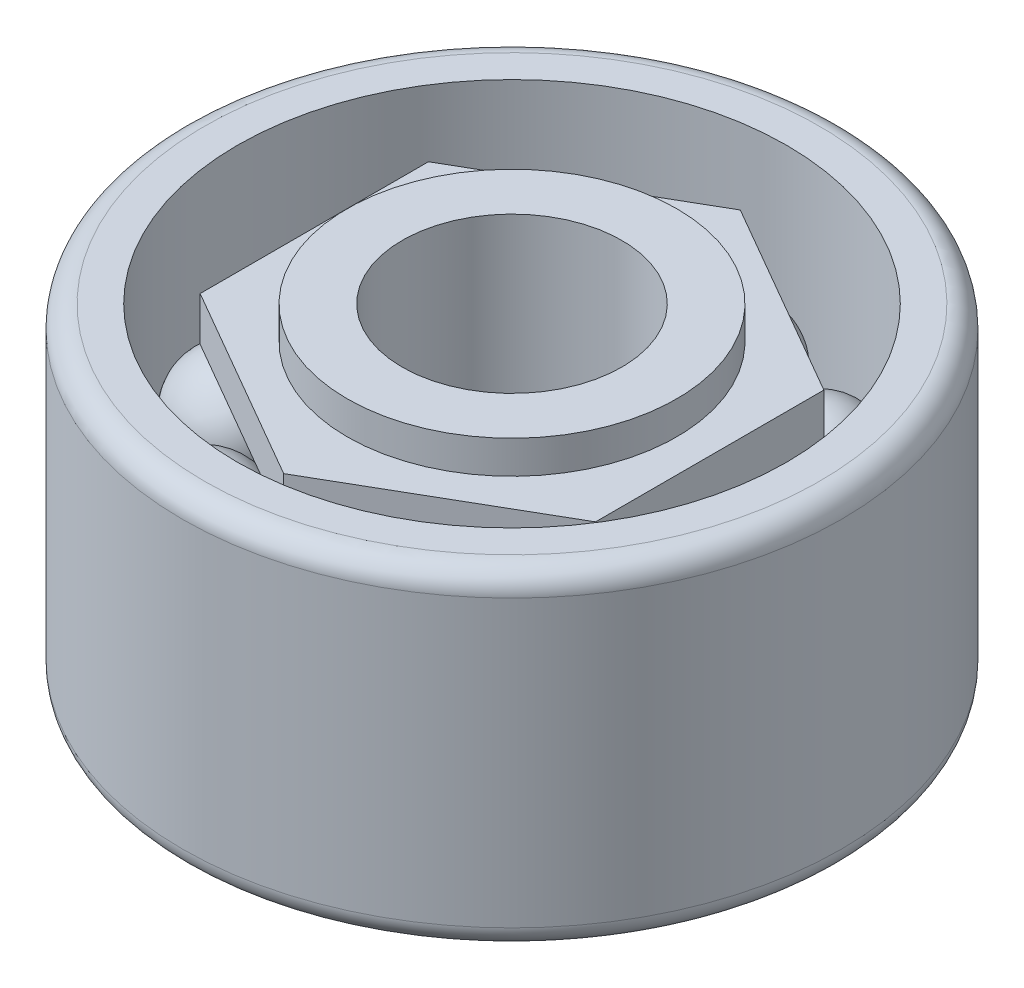
SolidWorks part; units mm, degrees
note: The reader was unsure of these and kept them because the rebuilt part matched: shared geometry of "Sketch1<3>", "Sketch1<4>".
ref_plane "Front Plane" through (0, 0, 0) normal (0, 0, 1) x (1, 0, 0)
ref_plane "Top Plane" through (0, 0, 0) normal (0, 1, 0) x (1, 0, 0)
ref_plane "Right Plane" through (0, 0, 0) normal (1, 0, 0) x (0, 0, -1)
sketch "Sketch1" plane through (0, 0, 0) normal (0, 1, 0) x (1, 0, 0)
  line L7 (-0.9, 0.5196) -> (-0.9, -0.5196)
  line L8 (-0.9, -0.5196) -> (0, -1.0392)
  line L9 (0, -1.0392) -> (0.9, -0.5196)
  line L10 (0.9, -0.5196) -> (0.9, 0.5196)
  line L11 (0.9, 0.5196) -> (0, 1.0392)
  line L12 (0, 1.0392) -> (-0.9, 0.5196)
  circle A0 centre (0, 0) radius 0.5
  circle A1 centre (0, 0) radius 0.9 construction
  circle A2 centre (0, 0) radius 0.75
  circle A3 centre (0, 0) radius 1.25
  circle A4 centre (0, 0) radius 1.5
  point P4 (0, 0)
  dimension "D1" = 1
  dimension "D2" = 0.25
  dimension "D3" = 0.25
  dimension "D4" = 3
  dimension "D5" = 1.8
extrude "Boss-Extrude1" add sketch "Sketch1" along normal mid plane 1.5 contours A2 A0 | A4 A3
extrude "Boss-Extrude2" add sketch "Sketch1<3>" along normal blind 0.2 from offset 0.4
sketch "Sketch1<3>" plane through (0, 0, 0) normal (0, 1, 0) x (1, 0, 0) same geometry as "Sketch1"
extrude "Boss-Extrude3" add sketch "Sketch1<4>" against normal blind 0.2 from offset 0.4 offset against normal yes
sketch "Sketch1<4>" plane through (0, 0, 0) normal (0, 1, 0) x (1, 0, 0) same geometry as "Sketch1"
sketch "Sketch2" plane through (0, 0, 0) normal (1, 0, 0) x (0, 0, -1)
  line L0 (-1000, 0) -> (49000, 0) construction
  line L1 (0.75, 0) -> (1.25, 0)
  line L2 (1.25, -0.75) -> (1.25, 0.75) construction
  line L3 (0.75, -0.4) -> (0.75, 0.4) construction
  arc A0 (0.75, 0) -> (1.25, 0) centre (1, 0) cw
  point P7 (0, 0)
revolve "Revolve1" add sketch "Sketch2" angle 360 about L1
pattern_circular "CirPattern4" count 10 over 360 about axis through (0, 0, 0) along (0, 1, 0) of bodies 105
fillet "Fillet1" radius 0.1 2 edges at (0, -0.75, 1.5) (0, 0.75, 1.5)
